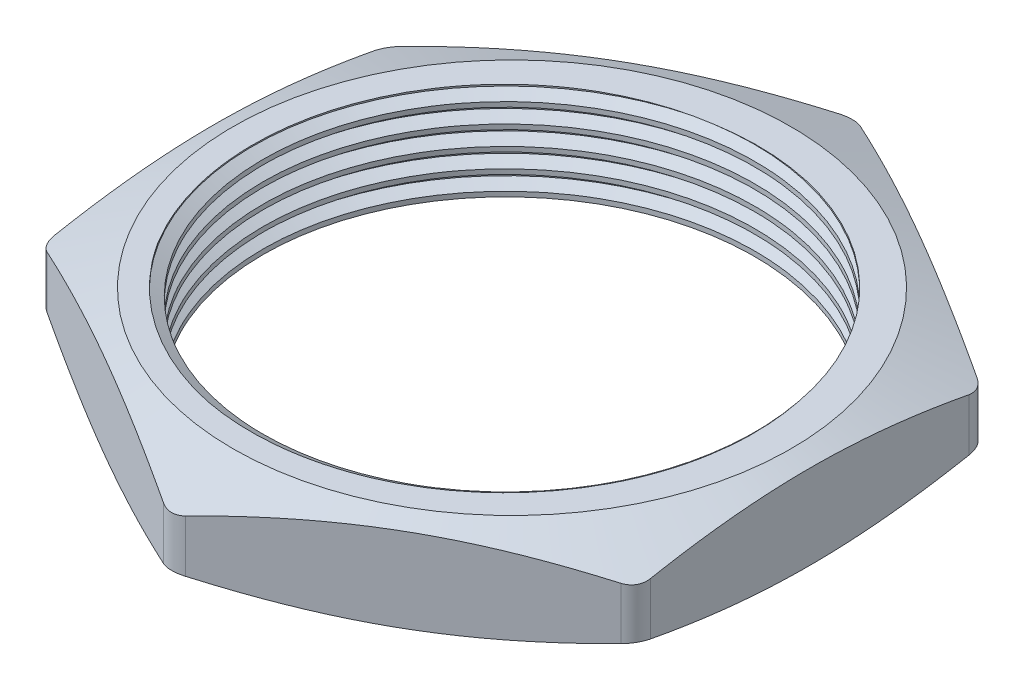
SolidWorks part; units mm, degrees
material "Никель"
ref_plane "Спереди" through (0, 0, 0) normal (0, 0, 1) x (1, 0, 0)
ref_plane "Сверху" through (0, 0, 0) normal (0, 1, 0) x (1, 0, 0)
ref_plane "Справа" through (0, 0, 0) normal (1, 0, 0) x (0, 0, -1)
ref_axis "Main" through (0, 7.4618, 0) along (0, -1, 0)
sketch "Эскиз1" plane through (0, 0, 0) normal (0, 1, 0) x (1, 0, 0)
  line L0 (0, 0) -> (0, 7.9674) construction
  line L1 (0, 7.9674) -> (-6.9, 3.9837)
  line L2 (-6.9, 3.9837) -> (-6.9, -3.9837)
  line L3 (-6.9, -3.9837) -> (0, -7.9674)
  line L4 (0, -7.9674) -> (6.9, -3.9837)
  line L5 (6.9, -3.9837) -> (6.9, 3.9837)
  line L6 (6.9, 3.9837) -> (0, 7.9674)
  circle A0 centre (0, 0) radius 6.9 construction
  circle A1 centre (0, 0) radius 5.7
  dimension "D2" = 11.4
  dimension "D1" = 13.8
extrude "Бобышка-Вытянуть1" add sketch "Эскиз1" along normal mid plane 2.3
sketch "Эскиз2" plane through (0, 0, 0) normal (1, 0, 0) x (0, 0, -1)
  line L0 (-7.9674, 0.55) -> (-7.9674, 1.15)
  line L1 (-7.9674, 1.15) -> (-7.9674, -1.15) construction
  line L2 (-7.9674, 1.15) -> (-6.4674, 1.15)
  line L3 (-7.9674, 1.15) -> (-3.9837, 1.15) construction
  line L4 (-6.4674, 1.15) -> (-7.9674, 0.55)
  line L5 (-7.9674, -0.55) -> (-7.9674, -1.15)
  line L6 (-7.9674, -1.15) -> (-6.4674, -1.15)
  line L7 (-7.9674, -1.15) -> (-3.9837, -1.15) construction
  line L8 (-6.4674, -1.15) -> (-7.9674, -0.55)
  line L9 (-6.4674, 1.15) -> (-6.4674, -1.15) construction
  dimension "D1" = 1.5
  dimension "D2" = 0.6
revolve "Вырез-Повернуть1" cut sketch "Эскиз2" angle 360 about axis through (0, 7.4618, 0) along (0, -1, 0)
fillet "Скругление1" radius 0.5 6 edges at (0, 0, -7.9674) (6.9, 0, -3.9837) (-6.9, 0, 3.9837) (-6.9, 0, -3.9837) (6.9, 0, 3.9837) (0, 0, 7.9674)
thread "Резьба1" pitch 0.45 method cut profile "Профиль резьбы2" start angle 0, offset 1, length 4, pitch 0.45, diameter 11.4
ref_plane "Плоскость2" through (-5.7, 2.15, 0) normal (0, 0, 1) x (-1, 0, 0)
sketch "Профиль резьбы2" plane through (-5.7, 2.15, 0) normal (0, 0, 1) x (-1, 0, 0)
  line L0 (0, 0) -> (0, 0.45) construction
  line L1 (0, 0) -> (0.2436, 0.1406)
  line L2 (0.2436, 0.1406) -> (0.2436, 0.1969)
  line L3 (0.2436, 0.1969) -> (0, 0.3375)
  line L4 (0.2436, 0.1687) -> (0, 0.1687) construction
  line L11 (0, 0) -> (0, 0.3375)
  point P2 (0, 0)
  dimension "Pitch" = 0.45
  dimension "Profile_Angle" = 60
  dimension "Profile_Land" = 0.0562
  dimension "Profile_Height" = 0.2436
